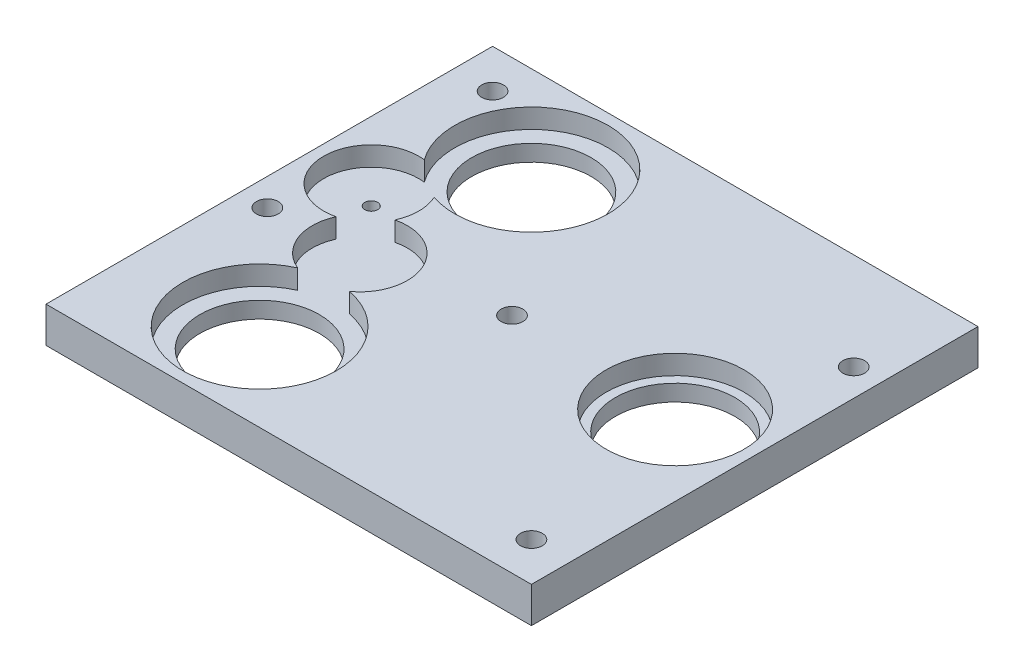
SolidWorks part; units mm, degrees
ref_plane "Front" through (0, 0, 0) normal (0, 0, 1) x (1, 0, 0)
ref_plane "Top" through (0, 0, 0) normal (0, 1, 0) x (1, 0, 0)
ref_plane "Right" through (0, 0, 0) normal (1, 0, 0) x (0, 0, -1)
sketch "Sketch1" plane through (0, 0, 0) normal (0, 1, 0) x (1, 0, 0)
  line L1 (-62.5, -57.5) -> (62.5, -57.5)
  line L2 (-62.5, -57.5) -> (-62.5, 57.5)
  line L3 (-62.5, 57.5) -> (62.5, 57.5)
  line L4 (62.5, -57.5) -> (62.5, 57.5)
  line L5 (-62.5, -57.5) -> (62.5, 57.5) construction
  line L6 (-62.5, 57.5) -> (62.5, -57.5) construction
  point P0 (0, 0)
  dimension "D1" = 125
  dimension "D2" = 115
extrude "Test_Base_Postion" add sketch "Sketch1" along normal blind 9.215
sketch "Thumb_Position" plane through (0, 9.215, 0) normal (0, 1, 0) x (1, 0, 0)
  line L0 (62.5, -57.5) -> (62.5, 57.5) construction
  line L1 (49, -12) -> (17, -12)
  line L2 (49, -12) -> (49, 43)
  line L3 (49, 43) -> (17, 43)
  line L4 (17, -12) -> (17, 43)
  line L5 (33, 43) -> (33, -12) construction
  line L6 (51, -12) -> (15, -12)
  line L7 (51, -12) -> (51, 12)
  line L8 (51, 12) -> (15, 12)
  line L9 (15, -12) -> (15, 12)
  line L10 (33, 12) -> (33, -12) construction
  line L12 (51, 0) -> (15, 0) construction
  circle A1 centre (42, 0) radius 9
  circle A2 centre (42, 0) radius 17.75 construction
  dimension "D6" = 18
  dimension "D7" = 20.5
  dimension "D5" = 35.5
  dimension "D1" = 55
  dimension "D2" = 32
  dimension "D3" = 36
  dimension "D4" = 24
sketch "Finger_Gears_Position" plane through (0, 0, 0) normal (0, -1, 0) x (1, 0, 0)
  line L0 (-30, 35) -> (-30, 52.5) construction
  line L1 (-30, 35) -> (-47.5, 35) construction
  line L2 (-30, -35) -> (-30, -52.5) construction
  line L3 (-30, -35) -> (-47.5, -35) construction
  line L4 (-62.5, -57.5) -> (-62.5, 57.5) construction
  line L5 (-62.5, 57.5) -> (62.5, 57.5) construction
  line L8 (62.5, -57.5) -> (-62.5, -57.5) construction
  line L9 (-62.5, 0) -> (62.5, 0) construction
  line L10 (62.5, 57.5) -> (62.5, -57.5) construction
  line L13 (-30, -35) -> (-43, -35) construction
  line L15 (-43, -51) -> (12, -51) construction
  line L16 (-43, -51) -> (-43, -19) construction
  line L17 (-43, -19) -> (12, -19) construction
  line L18 (12, -51) -> (12, -19) construction
  line L20 (-30, 35) -> (-43, 35) construction
  line L21 (12, -35) -> (-23, -35) construction
  line L22 (-43, 19) -> (12, 19) construction
  line L23 (-43, 19) -> (-43, 51) construction
  line L24 (-43, 51) -> (12, 51) construction
  line L25 (12, 19) -> (12, 51) construction
  line L26 (12, 35) -> (-23, 35) construction
  line L27 (-23, -35) -> (-23, 35) construction
  circle A0 centre (-30, 35) radius 17.5 construction
  circle A1 centre (-30, -35) radius 17.5 construction
  dimension "D1" = 35
  dimension "D2" = 15
  dimension "D3" = 5
  dimension "D4" = 5
  dimension "D5" = 13
  dimension "D6" = 55
  dimension "D7" = 32
  dimension "D8" = 13
  dimension "D9" = 55
  dimension "D10" = 32
  dimension "D11" = 35
  dimension "D12" = 35
sketch "Fingers_Position" plane through (0, 9.215, 0) normal (0, 1, 0) x (1, 0, 0)
  line L0 (12, 35) -> (-23, 35) construction
  line L1 (12, 19) -> (-43, 19)
  line L2 (12, 19) -> (12, 51)
  line L3 (12, 51) -> (-43, 51)
  line L4 (-43, 19) -> (-43, 51)
  line L5 (12, -51) -> (-43, -51)
  line L6 (12, -51) -> (12, -19)
  line L7 (12, -19) -> (-43, -19)
  line L8 (-43, -51) -> (-43, -19)
  line L9 (-23, 35) -> (-23, -35) construction
  line L10 (-23, -35) -> (12, -35) construction
sketch "Thumb_Knuckle_Mount_Position" plane through (0, 0, 0) normal (0, -1, 0) x (1, 0, 0)
  circle A0 centre (42, 0) radius 17.75
  dimension "D1" = 35.5
sketch "Gears_Position" plane through (0, 0, 0) normal (0, -1, 0) x (-1, 0, 0)
  line L0 (30, 35) -> (30, 14.5) construction
  line L1 (30, 35) -> (31.006, 17.5289) construction
  line L2 (31.21, 16.5396) -> (28.79, 16.5396) construction
  line L3 (31.9195, 14.5901) -> (30, 19.8639) construction
  line L4 (27.3242, 14.6754) -> (30, 35) construction
  line L5 (28.79, 16.5396) -> (26.3908, 16.8555) construction
  line L6 (30, -35) -> (30, -55.5) construction
  line L7 (31.21, -53.4604) -> (28.79, -53.4604) construction
  line L8 (31.006, -52.4711) -> (30, -35) construction
  line L9 (31.9195, -55.4099) -> (30, -50.1361) construction
  line L10 (30, -35) -> (27.3242, -55.3246) construction
  line L11 (28.79, -53.4604) -> (26.3908, -53.1445) construction
  line L12 (47.5, 11.2513) -> (47.5, -1.7487) construction
  line L13 (47.5, 11.2513) -> (48.507, 1.3021) construction
  line L14 (48.7316, 0.3205) -> (46.2684, 0.3205) construction
  line L15 (49.4322, -1.6043) -> (47.5, 3.7043) construction
  line L16 (47.5, 11.2513) -> (44.6072, -1.4227) construction
  line L17 (46.2684, 0.3205) -> (43.8669, 0.8686) construction
  line L18 (34.7162, -16.6374) -> (32.253, -16.6374) construction
  line L19 (33.4846, -5.7065) -> (30.5918, -18.3806) construction
  line L20 (32.253, -16.6374) -> (29.8515, -16.0892) construction
  line L21 (33.4846, -5.7065) -> (33.4846, -18.7065) construction
  line L22 (33.4846, -5.7065) -> (34.4916, -15.6557) construction
  line L23 (35.4168, -18.5621) -> (33.4846, -13.2535) construction
  line L24 (33.4846, -5.7065) -> (62.5, -5.7065) construction
  line L25 (62.5, 57.5) -> (62.5, -57.5) construction
  line L30 (33.4846, -5.7065) -> (33.4846, -57.5) construction
  line L31 (62.5, 57.5) -> (62.5, -57.5) construction
  line L33 (62.5, -57.5) -> (-62.5, -57.5) construction
  circle A0 centre (30, -35) radius 19.5 construction
  circle A1 centre (30, 35) radius 19.5 construction
  circle A2 centre (30, 35) radius 18.5
  circle A3 centre (30, 35) radius 17.5 construction
  circle A4 centre (30, 35) radius 20.5 construction
  arc A5 (32.787, 14.6903) -> (31.006, 17.5289) centre (34.4773, 17.7288) cw
  arc A6 (27.213, 14.6903) -> (28.994, 17.5289) centre (25.5227, 17.7288) ccw
  arc A7 (32.787, -55.3097) -> (31.006, -52.4711) centre (34.4773, -52.2712) cw
  arc A8 (27.213, -55.3097) -> (28.994, -52.4711) centre (25.5227, -52.2712) ccw
  circle A9 centre (30, -35) radius 18.5
  circle A10 centre (30, -35) radius 20.5 construction
  circle A11 centre (30, -35) radius 17.5 construction
  arc A12 (27.4355, -55.339) -> (26.4499, -52.1361) centre (29.8546, -52.8415) cw
  arc A13 (22.0515, -53.8963) -> (24.5064, -51.6154) centre (21.2052, -50.5239) ccw
  arc A14 (22.2587, -53.9822) -> (22.1357, -50.6334) centre (25.2419, -52.1959) cw
  arc A15 (17.4316, -51.1952) -> (20.3932, -49.6274) centre (17.487, -47.7186) ccw
  arc A16 (17.6096, -51.3318) -> (18.3575, -48.0653) centre (20.9534, -50.3785) cw
  arc A17 (13.6682, -47.3904) -> (16.9347, -46.6425) centre (14.6215, -44.0466) ccw
  arc A18 (13.8048, -47.5684) -> (15.3726, -44.6068) centre (17.2814, -47.513) cw
  arc A19 (11.0178, -42.7413) -> (14.3666, -42.8643) centre (12.8041, -39.7581) ccw
  arc A20 (11.1037, -42.9485) -> (13.3846, -40.4936) centre (14.4761, -43.7948) cw
  arc A21 (9.661, -37.5645) -> (12.8639, -38.5501) centre (12.1585, -35.1454) ccw
  arc A22 (9.6903, -37.787) -> (12.5289, -36.006) centre (12.7288, -39.4773) cw
  arc A23 (9.6903, -32.213) -> (12.5289, -33.994) centre (12.7288, -30.5227) ccw
  arc A24 (9.661, -32.4355) -> (12.8639, -31.4499) centre (12.1585, -34.8546) cw
  arc A25 (11.1037, -27.0515) -> (13.3846, -29.5064) centre (14.4761, -26.2052) ccw
  arc A26 (11.0178, -27.2587) -> (14.3666, -27.1357) centre (12.8041, -30.2419) cw
  arc A27 (13.8048, -22.4316) -> (15.3726, -25.3932) centre (17.2814, -22.487) ccw
  arc A28 (13.6682, -22.6096) -> (16.9347, -23.3575) centre (14.6215, -25.9534) cw
  arc A29 (17.6096, -18.6682) -> (18.3575, -21.9347) centre (20.9534, -19.6215) ccw
  arc A30 (17.4316, -18.8048) -> (20.3932, -20.3726) centre (17.487, -22.2814) cw
  arc A31 (22.2587, -16.0178) -> (22.1357, -19.3666) centre (25.2419, -17.8041) ccw
  arc A32 (22.0515, -16.1037) -> (24.5064, -18.3846) centre (21.2052, -19.4761) cw
  arc A33 (27.4355, -14.661) -> (26.4499, -17.8639) centre (29.8546, -17.1585) ccw
  arc A34 (27.213, -14.6903) -> (28.994, -17.5289) centre (25.5227, -17.7288) cw
  arc A35 (32.787, -14.6903) -> (31.006, -17.5289) centre (34.4773, -17.7288) ccw
  arc A36 (32.5645, -14.661) -> (33.5501, -17.8639) centre (30.1454, -17.1585) cw
  arc A37 (37.9485, -16.1037) -> (35.4936, -18.3846) centre (38.7948, -19.4761) ccw
  arc A38 (37.7413, -16.0178) -> (37.8643, -19.3666) centre (34.7581, -17.8041) cw
  arc A39 (42.5684, -18.8048) -> (39.6068, -20.3726) centre (42.513, -22.2814) ccw
  arc A40 (42.3904, -18.6682) -> (41.6425, -21.9347) centre (39.0466, -19.6215) cw
  arc A41 (46.3318, -22.6096) -> (43.0653, -23.3575) centre (45.3785, -25.9534) ccw
  arc A42 (46.1952, -22.4316) -> (44.6274, -25.3932) centre (42.7186, -22.487) cw
  arc A43 (48.9822, -27.2587) -> (45.6334, -27.1357) centre (47.1959, -30.2419) ccw
  arc A44 (48.8963, -27.0515) -> (46.6154, -29.5064) centre (45.5239, -26.2052) cw
  arc A45 (50.339, -32.4355) -> (47.1361, -31.4499) centre (47.8415, -34.8546) ccw
  arc A46 (50.3097, -32.213) -> (47.4711, -33.994) centre (47.2712, -30.5227) cw
  arc A47 (50.3097, -37.787) -> (47.4711, -36.006) centre (47.2712, -39.4773) ccw
  arc A48 (50.339, -37.5645) -> (47.1361, -38.5501) centre (47.8415, -35.1454) cw
  arc A49 (48.8963, -42.9485) -> (46.6154, -40.4936) centre (45.5239, -43.7948) ccw
  arc A50 (48.9822, -42.7413) -> (45.6334, -42.8643) centre (47.1959, -39.7581) cw
  arc A51 (46.1952, -47.5684) -> (44.6274, -44.6068) centre (42.7186, -47.513) ccw
  arc A52 (46.3318, -47.3904) -> (43.0653, -46.6425) centre (45.3785, -44.0466) cw
  arc A53 (42.3904, -51.3318) -> (41.6425, -48.0653) centre (39.0466, -50.3785) ccw
  arc A54 (42.5684, -51.1952) -> (39.6068, -49.6274) centre (42.513, -47.7186) cw
  arc A55 (37.7413, -53.9822) -> (37.8643, -50.6334) centre (34.7581, -52.1959) ccw
  arc A56 (37.9485, -53.8963) -> (35.4936, -51.6154) centre (38.7948, -50.5239) cw
  arc A57 (32.5645, -55.339) -> (33.5501, -52.1361) centre (30.1454, -52.8415) ccw
  arc A76 (27.4355, 14.661) -> (26.4499, 17.8639) centre (29.8546, 17.1585) cw
  arc A77 (22.0515, 16.1037) -> (24.5064, 18.3846) centre (21.2052, 19.4761) ccw
  arc A78 (22.2587, 16.0178) -> (22.1357, 19.3666) centre (25.2419, 17.8041) cw
  arc A79 (17.4316, 18.8048) -> (20.3932, 20.3726) centre (17.487, 22.2814) ccw
  arc A80 (17.6096, 18.6682) -> (18.3575, 21.9347) centre (20.9534, 19.6215) cw
  arc A81 (13.6682, 22.6096) -> (16.9347, 23.3575) centre (14.6215, 25.9534) ccw
  arc A82 (13.8048, 22.4316) -> (15.3726, 25.3932) centre (17.2814, 22.487) cw
  arc A83 (11.0178, 27.2587) -> (14.3666, 27.1357) centre (12.8041, 30.2419) ccw
  arc A84 (11.1037, 27.0515) -> (13.3846, 29.5064) centre (14.4761, 26.2052) cw
  arc A85 (9.661, 32.4355) -> (12.8639, 31.4499) centre (12.1585, 34.8546) ccw
  arc A86 (9.6903, 32.213) -> (12.5289, 33.994) centre (12.7288, 30.5227) cw
  arc A87 (9.6903, 37.787) -> (12.5289, 36.006) centre (12.7288, 39.4773) ccw
  arc A88 (9.661, 37.5645) -> (12.8639, 38.5501) centre (12.1585, 35.1454) cw
  arc A89 (11.1037, 42.9485) -> (13.3846, 40.4936) centre (14.4761, 43.7948) ccw
  arc A90 (11.0178, 42.7413) -> (14.3666, 42.8643) centre (12.8041, 39.7581) cw
  arc A91 (13.8048, 47.5684) -> (15.3726, 44.6068) centre (17.2814, 47.513) ccw
  arc A92 (13.6682, 47.3904) -> (16.9347, 46.6425) centre (14.6215, 44.0466) cw
  arc A93 (17.6096, 51.3318) -> (18.3575, 48.0653) centre (20.9534, 50.3785) ccw
  arc A94 (17.4316, 51.1952) -> (20.3932, 49.6274) centre (17.487, 47.7186) cw
  arc A95 (22.2587, 53.9822) -> (22.1357, 50.6334) centre (25.2419, 52.1959) ccw
  arc A96 (22.0515, 53.8963) -> (24.5064, 51.6154) centre (21.2052, 50.5239) cw
  arc A97 (27.4355, 55.339) -> (26.4499, 52.1361) centre (29.8546, 52.8415) ccw
  arc A98 (27.213, 55.3097) -> (28.994, 52.4711) centre (25.5227, 52.2712) cw
  arc A99 (32.787, 55.3097) -> (31.006, 52.4711) centre (34.4773, 52.2712) ccw
  arc A100 (32.5645, 55.339) -> (33.5501, 52.1361) centre (30.1454, 52.8415) cw
  arc A101 (37.9485, 53.8963) -> (35.4936, 51.6154) centre (38.7948, 50.5239) ccw
  arc A102 (37.7413, 53.9822) -> (37.8643, 50.6334) centre (34.7581, 52.1959) cw
  arc A103 (42.5684, 51.1952) -> (39.6068, 49.6274) centre (42.513, 47.7186) ccw
  arc A104 (42.3904, 51.3318) -> (41.6425, 48.0653) centre (39.0466, 50.3785) cw
  arc A105 (46.3318, 47.3904) -> (43.0653, 46.6425) centre (45.3785, 44.0466) ccw
  arc A106 (46.1952, 47.5684) -> (44.6274, 44.6068) centre (42.7186, 47.513) cw
  arc A107 (48.9822, 42.7413) -> (45.6334, 42.8643) centre (47.1959, 39.7581) ccw
  arc A108 (48.8963, 42.9485) -> (46.6154, 40.4936) centre (45.5239, 43.7948) cw
  arc A109 (50.339, 37.5645) -> (47.1361, 38.5501) centre (47.8415, 35.1454) ccw
  arc A110 (50.3097, 37.787) -> (47.4711, 36.006) centre (47.2712, 39.4773) cw
  arc A111 (50.3097, 32.213) -> (47.4711, 33.994) centre (47.2712, 30.5227) ccw
  arc A112 (50.339, 32.4355) -> (47.1361, 31.4499) centre (47.8415, 34.8546) cw
  arc A113 (48.8963, 27.0515) -> (46.6154, 29.5064) centre (45.5239, 26.2052) ccw
  arc A114 (48.9822, 27.2587) -> (45.6334, 27.1357) centre (47.1959, 30.2419) cw
  arc A115 (46.1952, 22.4316) -> (44.6274, 25.3932) centre (42.7186, 22.487) ccw
  arc A116 (46.3318, 22.6096) -> (43.0653, 23.3575) centre (45.3785, 25.9534) cw
  arc A117 (42.3904, 18.6682) -> (41.6425, 21.9347) centre (39.0466, 19.6215) ccw
  arc A118 (42.5684, 18.8048) -> (39.6068, 20.3726) centre (42.513, 22.2814) cw
  arc A119 (37.7413, 16.0178) -> (37.8643, 19.3666) centre (34.7581, 17.8041) ccw
  arc A120 (37.9485, 16.1037) -> (35.4936, 18.3846) centre (38.7948, 19.4761) cw
  arc A121 (32.5645, 14.661) -> (33.5501, 17.8639) centre (30.1454, 17.1585) ccw
  circle A140 centre (47.5, 11.2513) radius 10 construction
  circle A141 centre (47.5, 11.2513) radius 11
  circle A142 centre (47.5, 11.2513) radius 12 construction
  circle A143 centre (47.5, 11.2513) radius 13 construction
  arc A144 (50.0522, -1.4957) -> (48.507, 1.3021) centre (52.5541, 1.7118) cw
  arc A145 (44.9478, -1.4957) -> (46.493, 1.3021) centre (42.4459, 1.7118) ccw
  arc A146 (30.9324, -18.4535) -> (32.4776, -15.6557) centre (28.4305, -15.2461) ccw
  circle A147 centre (33.4846, -5.7065) radius 10 construction
  circle A148 centre (33.4846, -5.7065) radius 11
  arc A149 (36.0368, -18.4535) -> (34.4916, -15.6557) centre (38.5387, -15.2461) cw
  circle A150 centre (33.4846, -5.7065) radius 12 construction
  circle A151 centre (33.4846, -5.7065) radius 13 construction
  arc A152 (44.2688, -1.3407) -> (44.0905, 1.8505) centre (47.9145, 0.4636) cw
  arc A153 (39.6698, 0.874) -> (42.276, 2.7243) centre (38.8073, 4.8494) ccw
  arc A154 (39.1253, 1.3083) -> (40.3493, 4.2608) centre (43.1929, 1.352) cw
  arc A155 (35.9427, 5.2991) -> (39.0936, 5.8354) centre (36.8905, 9.255) ccw
  arc A156 (35.6405, 5.9266) -> (38.0243, 8.0557) centre (39.3243, 4.2012) cw
  arc A157 (34.5047, 10.9031) -> (37.5762, 10.0191) centre (37.075, 14.056) ccw
  arc A158 (34.5047, 11.5996) -> (37.5762, 12.4835) centre (37.075, 8.4467) cw
  arc A159 (35.6405, 16.576) -> (38.0243, 14.4469) centre (39.3243, 18.3015) ccw
  arc A160 (35.9427, 17.2035) -> (39.0936, 16.6672) centre (36.8905, 13.2477) cw
  arc A161 (39.1253, 21.1944) -> (40.3493, 18.2418) centre (43.1929, 21.1506) ccw
  arc A162 (39.6698, 21.6286) -> (42.276, 19.7783) centre (38.8073, 17.6533) cw
  arc A163 (44.2688, 23.8433) -> (44.0905, 20.6521) centre (47.9145, 22.0391) ccw
  arc A164 (44.9478, 23.9983) -> (46.493, 21.2005) centre (42.4459, 20.7909) cw
  arc A165 (50.0522, 23.9983) -> (48.507, 21.2005) centre (52.5541, 20.7909) ccw
  arc A166 (50.7312, 23.8433) -> (50.9095, 20.6521) centre (47.0855, 22.0391) cw
  arc A167 (55.3302, 21.6286) -> (52.724, 19.7783) centre (56.1927, 17.6533) ccw
  arc A168 (55.8747, 21.1944) -> (54.6507, 18.2418) centre (51.8071, 21.1506) cw
  arc A169 (59.0573, 17.2035) -> (55.9064, 16.6672) centre (58.1095, 13.2477) ccw
  arc A170 (59.3595, 16.576) -> (56.9757, 14.4469) centre (55.6757, 18.3015) cw
  arc A171 (60.4953, 11.5996) -> (57.4238, 12.4835) centre (57.925, 8.4467) ccw
  arc A172 (60.4953, 10.9031) -> (57.4238, 10.0191) centre (57.925, 14.056) cw
  arc A173 (59.3595, 5.9266) -> (56.9757, 8.0557) centre (55.6757, 4.2012) ccw
  arc A174 (59.0573, 5.2991) -> (55.9064, 5.8354) centre (58.1095, 9.255) cw
  arc A175 (55.8747, 1.3083) -> (54.6507, 4.2608) centre (51.8071, 1.352) ccw
  arc A176 (55.3302, 0.874) -> (52.724, 2.7243) centre (56.1927, 4.8494) cw
  arc A177 (50.7312, -1.3407) -> (50.9095, 1.8505) centre (47.0855, 0.4636) ccw
  arc A200 (25.6544, -16.0838) -> (28.2606, -14.2335) centre (24.7919, -12.1085) ccw
  arc A201 (30.2533, -18.2985) -> (30.0751, -15.1073) centre (33.8991, -16.4943) cw
  arc A202 (21.9273, -11.6587) -> (25.0782, -11.1225) centre (22.8751, -7.7029) ccw
  arc A203 (25.1099, -15.6496) -> (26.3339, -12.697) centre (29.1775, -15.6058) cw
  arc A204 (20.4893, -6.0548) -> (23.5608, -6.9387) centre (23.0596, -2.9019) ccw
  arc A205 (21.6251, -11.0312) -> (24.0089, -8.9021) centre (25.3089, -12.7567) cw
  arc A206 (21.6251, -0.3818) -> (24.0089, -2.5109) centre (25.3089, 1.3436) ccw
  arc A207 (20.4893, -5.3583) -> (23.5608, -4.4743) centre (23.0596, -8.5112) cw
  arc A208 (25.1099, 4.2365) -> (26.3339, 1.284) centre (29.1775, 4.1928) ccw
  arc A209 (21.9273, 0.2457) -> (25.0782, -0.2906) centre (22.8751, -3.7102) cw
  arc A210 (30.2533, 6.8855) -> (30.0751, 3.6943) centre (33.8991, 5.0812) ccw
  arc A211 (25.6544, 4.6708) -> (28.2606, 2.8205) centre (24.7919, 0.6954) cw
  arc A212 (36.0368, 7.0405) -> (34.4916, 4.2426) centre (38.5387, 3.833) ccw
  arc A213 (30.9324, 7.0405) -> (32.4776, 4.2426) centre (28.4305, 3.833) cw
  arc A214 (41.3148, 4.6708) -> (38.7086, 2.8205) centre (42.1773, 0.6954) ccw
  arc A215 (36.7158, 6.8855) -> (36.8941, 3.6943) centre (33.0701, 5.0812) cw
  arc A216 (45.0419, 0.2457) -> (41.891, -0.2906) centre (44.0941, -3.7102) ccw
  arc A217 (41.8593, 4.2365) -> (40.6353, 1.284) centre (37.7917, 4.1928) cw
  arc A218 (46.4799, -5.3583) -> (43.4084, -4.4743) centre (43.9096, -8.5112) ccw
  arc A219 (45.3441, -0.3818) -> (42.9602, -2.5109) centre (41.6603, 1.3436) cw
  arc A220 (45.3441, -11.0312) -> (42.9602, -8.9021) centre (41.6603, -12.7567) ccw
  arc A221 (46.4799, -6.0548) -> (43.4084, -6.9387) centre (43.9096, -2.9019) cw
  arc A222 (41.8593, -15.6496) -> (40.6353, -12.697) centre (37.7917, -15.6058) ccw
  arc A223 (45.0419, -11.6587) -> (41.891, -11.1225) centre (44.0941, -7.7029) cw
  arc A224 (36.7158, -18.2985) -> (36.8941, -15.1073) centre (33.0701, -16.4943) ccw
  arc A225 (41.3148, -16.0838) -> (38.7086, -14.2335) centre (42.1773, -12.1085) cw
  point P233 (30, -35)
  point P426 (30, 35)
  point P607 (47.5, 11.2513)
  point P753 (33.4846, -5.7065)
  dimension "D1" = 39
  dimension "D2" = 35
  dimension "D3" = 37
  dimension "D4" = 41
  dimension "D7" = 41
  dimension "D8" = 37
  dimension "D9" = 35
  dimension "D14" = 20
  dimension "D15" = 22
  dimension "D16" = 24
  dimension "D17" = 26
  dimension "D20" = 20
  dimension "D21" = 22
  dimension "D22" = 24
  dimension "D23" = 26
  dimension "D5" = 20
  dimension "D6" = 7.5
  dimension "D10" = 20
  dimension "D11" = 7.5
  dimension "D18" = 20
  dimension "D19" = 12.857
  dimension "D24" = 20
  dimension "D25" = 12.857
  dimension "D31" = 15
  dimension "D12" = 24
  dimension "D13" = 24
  dimension "D26" = 14
  dimension "D27" = 14
sketch "Sketch7" plane through (0, 0, 0) normal (0, -1, 0) x (1, 0, 0)
  circle A0 centre (42, 0) radius 17.75
  dimension "D1" = 35.5
extrude "Thumb_Knuckle_Mount" cut sketch "Sketch7" against normal up to surface (9.215 mm away) from offset 4.215 up to face at (0, 9.215, 0) offset against normal yes
sketch "Sketch8" plane through (0, 0, 0) normal (0, -1, 0) x (1, 0, 0)
  circle A0 centre (42, 0) radius 15.375
  dimension "D1" = 30.75
extrude "Thumb_Knuckle" cut sketch "Sketch8" along direction (0, -1, 0) on the side against the normal up to surface (4.215 mm away) up to face at (42, 4.215, -17.75)
sketch "Sketch10" plane through (0, 0, 0) normal (0, -1, 0) x (1, 0, 0)
  circle A0 centre (-30, 35) radius 19.75
  circle A1 centre (-33.4846, 5.7065) radius 12.25
  circle A2 centre (-47.5, -11.2513) radius 12.25
  circle A3 centre (-30, -35) radius 19.75
  dimension "D1" = 39.5
  dimension "D2" = 24.5
extrude "Gears_Position_Extrude_Cut" cut sketch "Sketch10" against normal up to surface (9.215 mm away) from offset 4.215 contours A1 A0 | A2 A1 A0 | A3 A2 A1 | A2 A3 | A0 A1 | A1 A2 | A2 A3 region at (-29.9633, 0, 35.3088) region at (-32.1923, 0, 16.5704) region at (-33.251, 0, 5.5556) region at (-40.4923, 0, -2.7724) region at (-48.0965, 0, -11.1962) region at (-41.0099, 0, -20.0588) region at (-29.8155, 0, -35.2503) up to face at (42, 9.215, -17.75) offset against normal yes
sketch "Sketch11" plane through (0, 0, 0) normal (0, -1, 0) x (1, 0, 0)
  circle A0 centre (-30, 35) radius 15.375
  circle A1 centre (-30, -35) radius 15.375
  circle A2 centre (-47.5, -11.2513) radius 1.65
  circle A3 centre (-30, 35) radius 19.75 construction
  circle A4 centre (-30, -35) radius 19.75 construction
  circle A5 centre (-47.5, -11.2513) radius 12.25 construction
  dimension "D1" = 3.3
  dimension "D2" = 30.75
extrude "Fingers_Knuckle_Mount_and_Intermediate_Through_Hole" cut sketch "Sketch11" against normal through all
sketch "Sketch12" plane through (0, 9.215, 0) normal (0, 1, 0) x (1, 0, 0)
  line L0 (-62.5, 57.5) -> (-52.5, 57.5) construction
  line L1 (62.5, 57.5) -> (-62.5, 57.5) construction
  line L2 (-52.5, 57.5) -> (-52.5, 47.5) construction
  line L3 (62.5, -57.5) -> (52.5, -57.5) construction
  line L4 (-62.5, -57.5) -> (62.5, -57.5) construction
  line L5 (52.5, -57.5) -> (52.5, -47.5) construction
  line L6 (62.5, 57.5) -> (62.5, 32.5) construction
  line L7 (62.5, -57.5) -> (62.5, 57.5) construction
  line L8 (62.5, 32.5) -> (55.5, 32.5) construction
  line L9 (-62.5, -57.5) -> (-62.5, -7.5) construction
  line L10 (-62.5, 57.5) -> (-62.5, -57.5) construction
  line L11 (-62.5, -7.5) -> (-55.5, -7.5) construction
  line L12 (-62.5, 0) -> (62.5, 0) construction
  line L13 (0, 57.5) -> (0, -57.5) construction
  circle A0 centre (-52.5, 47.5) radius 2.8
  circle A1 centre (55.5, 32.5) radius 2.8
  circle A2 centre (52.5, -47.5) radius 2.8
  circle A3 centre (-55.5, -7.5) radius 2.8
  circle A4 centre (0, 0) radius 2.8
  dimension "D1" = 5.6
  dimension "D2" = 10
  dimension "D3" = 10
  dimension "D4" = 50
  dimension "D5" = 7
  dimension "D6" = 10
  dimension "D7" = 10
  dimension "D8" = 25
  dimension "D9" = 7
extrude "Connect_Holes" cut sketch "Sketch12" against normal through all
equation "\"D6@Gears_Position\"=180/24"
equation "\"D11@Gears_Position\"=180/24"
equation "\"D19@Gears_Position\"=180/14"
equation "\"D25@Gears_Position\"=180/14"
